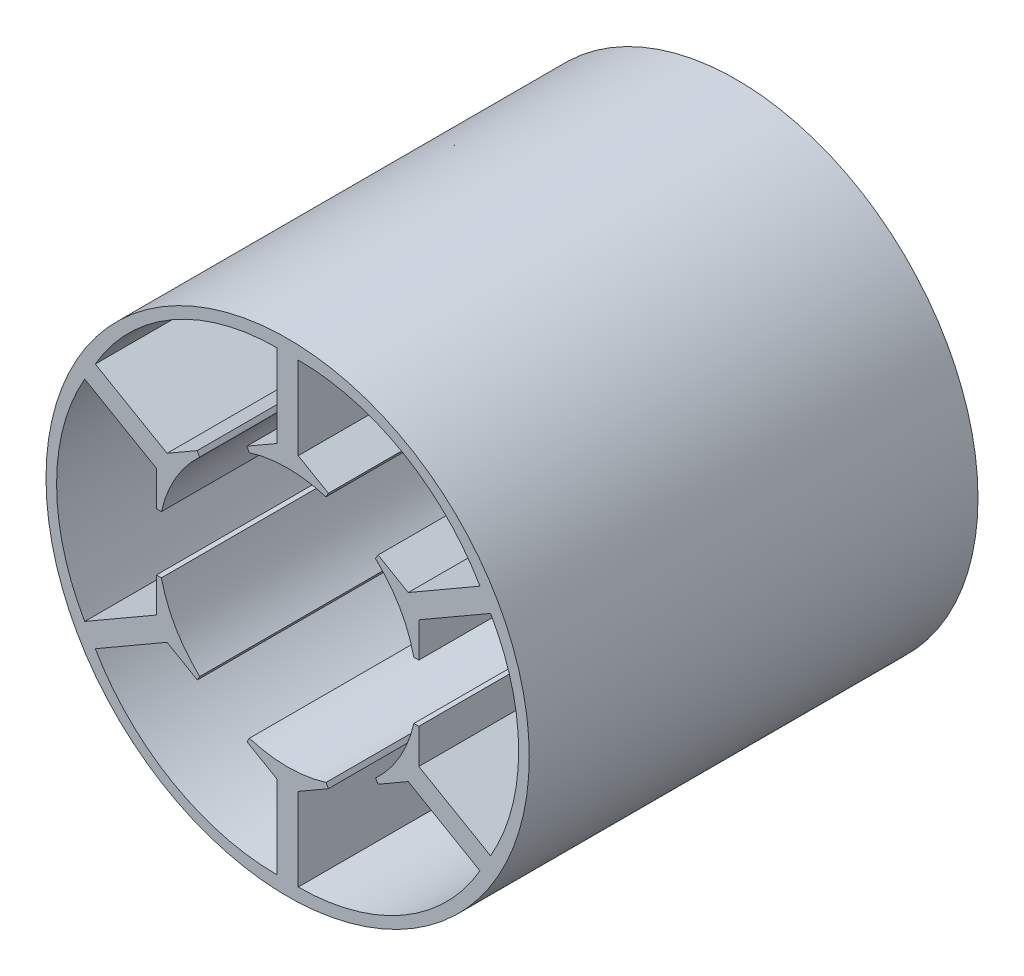
SolidWorks part; units mm, degrees
ref_plane "Front Plane" through (0, 0, 0) normal (0, 0, 1) x (1, 0, 0)
ref_plane "Top Plane" through (0, 0, 0) normal (0, 1, 0) x (1, 0, 0)
ref_plane "Right Plane" through (0, 0, 0) normal (1, 0, 0) x (0, 0, -1)
sketch "Motor_Base" plane through (0, 0, 0) normal (0, 0, 1) x (1, 0, 0)
  line L0 (0, 0) -> (0, 37.1463) construction
  line L1 (1.5331, 21.0694) -> (1.5331, 33.0694)
  line L2 (-1.5331, 21.0694) -> (-1.5331, 33.0694)
  line L3 (17.468, 11.8694) -> (27.8603, 17.8694)
  line L4 (19.0011, 9.214) -> (29.3934, 15.214)
  line L5 (19.0011, -9.186) -> (29.3934, -15.186)
  line L6 (17.468, -11.8414) -> (27.8603, -17.8414)
  line L7 (1.5331, -21.0414) -> (1.5331, -33.0414)
  line L8 (-1.5331, -21.0414) -> (-1.5331, -33.0414)
  line L9 (-17.468, -11.8414) -> (-27.8603, -17.8414)
  line L10 (-19.0011, -9.186) -> (-29.3934, -15.186)
  line L11 (-19.0011, 9.214) -> (-29.3934, 15.214)
  line L12 (-17.468, 11.8694) -> (-27.8603, 17.8694)
  line L13 (1.5331, 21.0694) -> (17.468, 11.8694)
  line L14 (-17.468, 11.8694) -> (-1.5331, 21.0694)
  line L15 (-19.0011, 9.214) -> (-19.0011, -9.186)
  line L16 (-17.468, -11.8414) -> (-1.5331, -21.0414)
  line L17 (1.5331, -21.0414) -> (17.468, -11.8414)
  line L18 (19.0011, -9.186) -> (19.0011, 9.214)
  line L20 (-9.5005, 16.4694) -> (-20.4004, 35.3485) construction
  line L23 (5.5682, 18.7398) -> (9.5005, 16.4694)
  line L25 (-15.9932, 24.7209) -> (-18.2032, 28.0912)
  line L27 (-13.4002, 26.2179) -> (-15.2139, 29.8171)
  line L28 (-15.9932, 24.7209) -> (-13.4002, 26.2179)
  line L29 (13.4123, 26.2109) -> (16.0053, 24.7139)
  line L30 (13.4123, 26.2109) -> (15.2261, 29.8101)
  line L31 (16.0053, 24.7139) -> (18.2154, 28.0842)
  line L32 (29.4055, 1.4901) -> (29.4055, -1.5041)
  line L33 (29.4055, 1.4901) -> (33.4293, 1.7189)
  line L34 (29.4055, -1.5041) -> (33.4293, -1.7329)
  line L35 (15.9932, -24.7209) -> (13.4002, -26.2179)
  line L36 (15.9932, -24.7209) -> (18.2032, -28.0912)
  line L37 (13.4002, -26.2179) -> (15.2139, -29.8171)
  line L38 (-13.4123, -26.2109) -> (-16.0053, -24.7139)
  line L39 (-13.4123, -26.2109) -> (-15.2261, -29.8101)
  line L40 (-16.0053, -24.7139) -> (-18.2154, -28.0842)
  line L41 (-29.4055, -1.4901) -> (-29.4055, 1.5041)
  line L42 (-29.4055, -1.4901) -> (-33.4293, -1.7189)
  line L43 (-29.4055, 1.5041) -> (-33.4293, 1.7329)
  line L44 (-15.9932, 24.7209) -> (-13.4002, 26.2179)
  line L45 (-13.0945, 14.3944) -> (-12.7312, 13.7651)
  line L46 (-5.9065, 18.5444) -> (-5.5432, 17.9151)
  line L47 (5.9187, 18.5374) -> (5.5553, 17.9081)
  line L49 (13.1067, 14.3874) -> (12.7434, 13.7581)
  line L50 (19.0011, 4.143) -> (18.2866, 4.143)
  line L52 (19.0011, -4.157) -> (18.2866, -4.157)
  line L53 (13.0824, -14.3734) -> (12.7312, -13.7651)
  line L55 (5.8944, -18.5234) -> (5.5432, -17.9151)
  line L56 (-5.9065, -18.5164) -> (-5.5553, -17.9081)
  line L58 (-13.0945, -14.3664) -> (-12.7434, -13.7581)
  line L59 (-19.0011, -4.143) -> (-18.2866, -4.143)
  line L61 (-19.0011, 4.157) -> (-18.2866, 4.157)
  circle A0 centre (0, 0) radius 35
  circle A4 centre (0, 0) radius 3.175
  circle A5 centre (0, 0) radius 18.75
  arc A6 (1.5331, 33.0694) -> (27.8603, 17.8694) centre (1.5331, 2.6694) cw
  circle A7 centre (0, 0) radius 4.7625
  arc A9 (29.3934, 15.214) -> (29.3934, -15.186) centre (3.0662, 0.014) cw
  arc A10 (27.8603, -17.8414) -> (1.5331, -33.0414) centre (1.5331, -2.6414) cw
  arc A11 (-1.5331, -33.0414) -> (-27.8603, -17.8414) centre (-1.5331, -2.6414) cw
  arc A12 (-29.3934, 15.214) -> (-29.3934, -15.186) centre (-3.0662, 0.014) ccw
  arc A13 (-27.8603, 17.8694) -> (-1.5331, 33.0694) centre (-1.5331, 2.6694) cw
  point P17 (0, 0)
  point P35 (0, 0.014)
  point P42 (9.5005, 16.4694)
  point P73 (0, 0)
  point P74 (-10.8113, 18.7398)
  point P99 (0, 0)
  dimension "D1" = 70
  dimension "D3" = 9.525
  dimension "D2" = 6.35
  dimension "D5" = 6
  dimension "D6" = 18.4
  dimension "D7" = 6
  dimension "D4" = 37.5
extrude "Stator_Shell" add sketch "Motor_Base" along normal blind 65 contours A0 | L18 L4 A9 L5 | A6 L3 L13 L1 | A10 L7 L17 L6 | A11 L9 L16 L8 | A12 L10 L15 L11 | A13 L2 L14 L12
extrude "Cut-Extrude1" cut sketch "Motor_Base<4>" along normal through all contours A5 A7 | A4 | A7 A4 region at (13.3758, 12.3711, 0) region at (0, 0, 0) region at (-4.6278, 0, 0)
sketch "Motor_Base<4>" plane through (0, 0, 0) normal (0, 0, 1) x (1, 0, 0) same geometry as "Motor_Base"
sketch "Stator_Lam_Support" plane through (0, 0, 0) normal (0, 0, -1) x (-1, 0, 0)
  line L0 (9.5005, 16.4694) -> (24.2852, 42.0991) construction
  line L1 (17.468, 11.8694) -> (1.5331, 21.0694) construction
  line L2 (14.3513, 31.3063) -> (13.5066, 28.0964)
  line L3 (13.5066, 28.0964) -> (17.56, 25.7582)
  line L4 (19.9157, 28.0964) -> (17.56, 25.7582)
  line L5 (34.2877, 3.2246) -> (31.0855, 2.3512)
  line L6 (34.2901, -3.1993) -> (31.0872, -2.3283)
  line L7 (31.0855, 2.3512) -> (31.0872, -2.3283)
  line L8 (19.9364, -28.0818) -> (17.579, -25.7452)
  line L9 (14.3744, -31.2957) -> (13.5273, -28.0865)
  line L10 (17.579, -25.7452) -> (13.5273, -28.0865)
  line L11 (-14.3513, -31.3063) -> (-13.5066, -28.0964)
  line L12 (-19.9157, -28.0964) -> (-17.56, -25.7582)
  line L13 (-13.5066, -28.0964) -> (-17.56, -25.7582)
  line L14 (-34.2877, -3.2246) -> (-31.0855, -2.3512)
  line L15 (-34.2901, 3.1993) -> (-31.0872, 2.3283)
  line L16 (-31.0855, -2.3512) -> (-31.0872, 2.3283)
  line L17 (-19.9364, 28.0818) -> (-17.579, 25.7452)
  line L18 (-14.3744, 31.2957) -> (-13.5273, 28.0865)
  line L19 (-17.579, 25.7452) -> (-13.5273, 28.0865)
  arc A0 (14.3513, 31.3063) -> (19.9157, 28.0964) centre (0, 0) cw
  arc A2 (34.2877, 3.2246) -> (34.2901, -3.1993) centre (0, 0) cw
  arc A3 (19.9364, -28.0818) -> (14.3744, -31.2957) centre (0, 0) cw
  arc A4 (-14.3513, -31.3063) -> (-19.9157, -28.0964) centre (0, 0) cw
  arc A5 (-34.2877, -3.2246) -> (-34.2901, 3.1993) centre (0, 0) cw
  arc A6 (-19.9364, 28.0818) -> (-14.3744, 31.2957) centre (0, 0) cw
  point P8 (1.5331, 33.0694)
  point P11 (15.5333, 26.9273)
  point P35 (0, 0)
  point P36 (0, 0)
extrude "Stator Lamination Support" add sketch "Stator_Lam_Support" against normal blind 16.35
sketch "Sketch6" plane through (0, 0, 65) normal (0, 0, 1) x (1, 0, 0)
  line L0 (9.5005, 16.4694) -> (18.75, 32.5036) construction
  line L1 (1.5331, 21.0694) -> (17.468, 11.8694) construction
  line L2 (14.4053, 16.6666) -> (11.564, 11.7412)
  line L3 (7.2157, 20.8139) -> (14.4053, 16.6666)
  line L4 (11.564, 11.7412) -> (4.3745, 15.8885)
  line L5 (4.3745, 15.8885) -> (7.2157, 20.8139)
  line L6 (21.6333, 4.158) -> (21.6363, -4.142)
  line L7 (15.9471, 4.1559) -> (21.6333, 4.158)
  line L8 (21.6363, -4.142) -> (15.9502, -4.1441)
  line L9 (15.9502, -4.1441) -> (15.9471, 4.1559)
  line L10 (14.4175, -16.656) -> (7.2311, -20.8086)
  line L11 (11.5727, -11.7327) -> (14.4175, -16.656)
  line L12 (7.2311, -20.8086) -> (4.3862, -15.8853)
  line L13 (4.3862, -15.8853) -> (11.5727, -11.7327)
  line L14 (-7.2157, -20.8139) -> (-14.4053, -16.6666)
  line L15 (-4.3745, -15.8885) -> (-7.2157, -20.8139)
  line L16 (-14.4053, -16.6666) -> (-11.564, -11.7412)
  line L17 (-11.564, -11.7412) -> (-4.3745, -15.8885)
  line L18 (-21.6333, -4.158) -> (-21.6363, 4.142)
  line L19 (-15.9471, -4.1559) -> (-21.6333, -4.158)
  line L20 (-21.6363, 4.142) -> (-15.9502, 4.1441)
  line L21 (-15.9502, 4.1441) -> (-15.9471, -4.1559)
  line L22 (-14.4175, 16.656) -> (-7.2311, 20.8086)
  line L23 (-11.5727, 11.7327) -> (-14.4175, 16.656)
  line L24 (-7.2311, 20.8086) -> (-4.3862, 15.8853)
  line L25 (-4.3862, 15.8853) -> (-11.5727, 11.7327)
  point P7 (10.8105, 18.7403)
  point P32 (0, 0)
  dimension "D1" = 4.15
extrude "Cut-Extrude3" cut sketch "Sketch6" against normal through all
